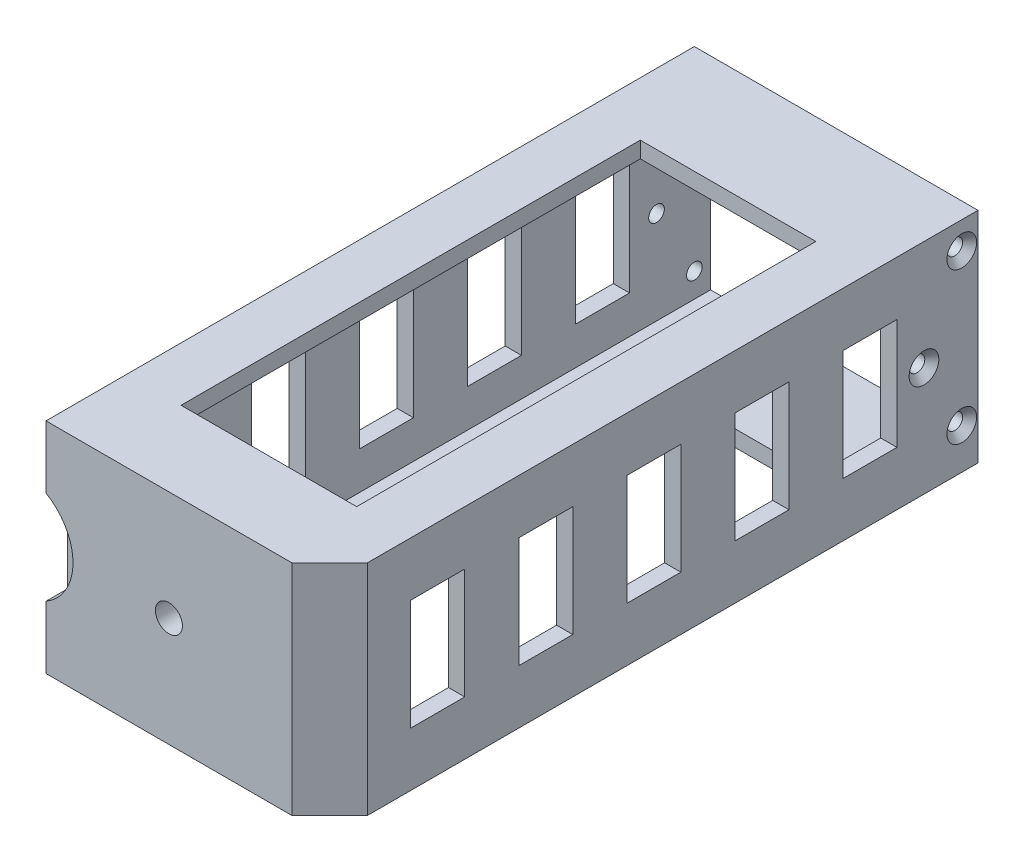
SolidWorks part; units mm, degrees
ref_plane "Plan de face" through (0, 0, 0) normal (0, 0, 1) x (1, 0, 0)
ref_plane "Plan de dessus" through (0, 0, 0) normal (0, 1, 0) x (1, 0, 0)
ref_plane "Plan de droite" through (0, 0, 0) normal (1, 0, 0) x (0, 0, -1)
sketch "Main-Sketch" plane through (0, 0, 0) normal (0, 0, 1) x (1, 0, 0)
  line L1 (-26.25, -20.25) -> (26.25, -20.25)
  line L2 (-26.25, -20.25) -> (-26.25, 20.25)
  line L3 (-26.25, 20.25) -> (26.25, 20.25)
  line L4 (26.25, -20.25) -> (26.25, 20.25)
  point P4 (-26.25, 0)
  point P6 (0, -20.25)
  dimension "D1" = 52.5
  dimension "D2" = 40.5
extrude "Main-Extrusion" add sketch "Main-Sketch" along normal blind 120
ref_plane "Plan1" through (0, 0, 112) normal (0, 0, 1) x (1, 0, 0)
sketch "Main-Hole-Sketch" plane through (0, 0, 0) normal (0, 0, -1) x (-1, 0, 0)
  line L0 (-26.25, -20.25) -> (-26.25, 20.25) construction
  line L1 (-23.25, 17.25) -> (23.25, 17.25)
  line L2 (-23.25, 17.25) -> (-23.25, -17.25)
  line L3 (-23.25, -17.25) -> (23.25, -17.25)
  line L4 (23.25, 17.25) -> (23.25, -17.25)
  line L5 (-26.25, 20.25) -> (26.25, 20.25) construction
  line L6 (26.25, 20.25) -> (26.25, -20.25) construction
  line L7 (26.25, -20.25) -> (-26.25, -20.25) construction
  point P4 (-23.25, 0)
  point P7 (-26.25, 0)
  point P8 (0, 17.25)
  point P11 (0, 20.25)
  dimension "D1" = 34.5
  dimension "D2" = 46.5
  dimension "D3" = 3
  dimension "D4" = 3
  dimension "D5" = 3
  dimension "D6" = 3
extrude "Main-Hole" cut sketch "Main-Hole-Sketch" against normal up to surface (112 mm away) up to plane "Plan1"
hole_wizard "Fraisage pour vis à tête fraisée M2.51" positions "Esquisse4" profile "Esquisse3" countersink size "M2.5" standard "Ansi Metric" end condition through all
sketch "Esquisse4" plane through (26.25, 0, 0) normal (1, 0, 0) x (0, 0, -1)
  line L0 (0, -20.25) -> (0, 20.25) construction
  line L1 (-112, 22.275) -> (-112, -22.275) construction
  point P0 (-10, 0)
  point P3 (0, 0)
  dimension "D2" = 102
sketch "Esquisse3" plane through (26.25, 0, 10) normal (0, 1, 0) x (0, 0, -1)
  line L0 (0, 0) -> (0, 52.5)
  line L1 (0, 52.5) -> (1.45, 52.5)
  line L2 (1.45, 52.5) -> (1.45, 1.3)
  line L3 (1.45, 1.3) -> (2.75, 0)
  line L5 (2.75, 0) -> (0, 0)
  line L6 (-1.45, 1.3) -> (-2.75, 0) construction
  line L11 (0, -6.35) -> (0, 107.95) construction
  dimension "Diamètre du perçage jusqu'au prochain" = 2.9
  dimension "Profondeur du perçage jusqu'au prochain" = 52.5
  dimension "Diamètre du fraisage entrant" = 5.5
  dimension "Angle du fraisage entrant" = 90
sketch "Esquisse6" plane through (26.25, 0, 0) normal (1, 0, 0) x (0, 0, -1)
  line L1 (-105, 10.25) -> (-95, 10.25)
  line L2 (-105, 10.25) -> (-105, -10.25)
  line L3 (-105, -10.25) -> (-95, -10.25)
  line L4 (-95, 10.25) -> (-95, -10.25)
  line L5 (-120, 20.25) -> (0, 20.25) construction
  line L6 (-120, -20.25) -> (0, -20.25) construction
  line L8 (-120, -20.25) -> (-120, 20.25) construction
  dimension "D1" = 10
  dimension "D2" = 10
  dimension "D3" = 10
  dimension "D4" = 15
extrude "Enlèv. mat.-Extru.3" cut sketch "Esquisse6" against normal through all
sketch "Esquisse7" plane through (0, 20.25, 0) normal (0, 1, 0) x (1, 0, 0)
  line L0 (-26.25, -120) -> (-26.25, 0) construction
  line L1 (-16.25, -105) -> (16.25, -105)
  line L2 (-16.25, -105) -> (-16.25, -20)
  line L3 (-16.25, -20) -> (16.25, -20)
  line L4 (16.25, -105) -> (16.25, -20)
  line L5 (26.25, -120) -> (26.25, 0) construction
  line L6 (26.25, 0) -> (-26.25, 0) construction
  line L7 (26.25, -120) -> (-26.25, -120) construction
  dimension "D1" = 10
  dimension "D2" = 10
  dimension "D3" = 20
  dimension "D4" = 15
extrude "Enlèv. mat.-Extru.4" cut sketch "Esquisse7" against normal through all
pattern_linear "Répétition linéaire1" count 5 spacing 20 along (0, 0, -1) of "Enlèv. mat.-Extru.3"
sketch "Esquisse8" plane through (0, 20.25, 0) normal (0, 1, 0) x (-1, 0, 0)
  line L0 (-19.25, 120) -> (-26.25, 113)
  line L1 (-26.25, 120) -> (26.25, 120) construction
  line L2 (-26.25, 120) -> (-26.25, 0) construction
  line L3 (-19.25, 120) -> (-26.25, 120)
  line L4 (-26.25, 120) -> (-26.25, 113)
  dimension "D1" = 45
  dimension "D2" = 45.5
extrude "Enlèv. mat.-Extru.5" cut sketch "Esquisse8" against normal through all
sketch "Esquisse10" plane through (0, 0, 120) normal (0, 0, 1) x (1, 0, 0)
  line L0 (-26.25, -20.25) -> (-26.25, 20.25) construction
  circle A0 centre (-31.25, 0) radius 10
  point P2 (-29.641, 0)
  point P5 (-26.25, 0)
  dimension "D2" = 20
  dimension "D1" = 5
extrude "Enlèv. mat.-Extru.7" cut sketch "Esquisse10" against normal blind 4
hole_wizard "Fraisage pour vis à tête fraisée M2.52" positions "Esquisse11" profile "Esquisse12" countersink size "M2.5" standard "Ansi Metric" end condition through all
sketch "Esquisse11" plane through (26.25, 0, 0) normal (1, 0, 0) x (0, 0, -1)
  line L0 (0, -20.25) -> (0, 20.25) construction
  line L1 (-113, 20.25) -> (0, 20.25) construction
  point P0 (-3, 15.25)
  dimension "D1" = 3
  dimension "D2" = 5
sketch "Esquisse12" plane through (26.25, 15.25, 3) normal (0, 1, 0) x (0, 0, -1)
  line L0 (0, 0) -> (0, 52.5)
  line L1 (0, 52.5) -> (1.45, 52.5)
  line L2 (1.45, 52.5) -> (1.45, 1.3)
  line L3 (1.45, 1.3) -> (2.75, 0)
  line L5 (2.75, 0) -> (0, 0)
  line L6 (-1.45, 1.3) -> (-2.75, 0) construction
  line L11 (0, -6.35) -> (0, 107.95) construction
  dimension "Diamètre du perçage jusqu'au prochain" = 2.9
  dimension "Profondeur du perçage jusqu'au prochain" = 52.5
  dimension "Diamètre du fraisage entrant" = 5.5
  dimension "Angle du fraisage entrant" = 90
pattern_linear "Répétition linéaire3" count 2 spacing 28 along (0, -1, 0) of "Fraisage pour vis à tête fraisée M2.52"
sketch "Esquisse13" plane through (0, 0, 120) normal (0, 0, 1) x (1, 0, 0)
  line L0 (19.25, 20.25) -> (-26.25, 20.25) construction
  line L1 (19.25, -20.25) -> (19.25, 20.25) construction
  circle A0 centre (-3.5, 0) radius 2.5
  point P2 (0, 0)
  point P5 (-3.5, 20.25)
  point P8 (19.25, 0)
  dimension "D1" = 5
extrude "Enlèv. mat.-Extru.8" cut sketch "Esquisse13" against normal up to next
